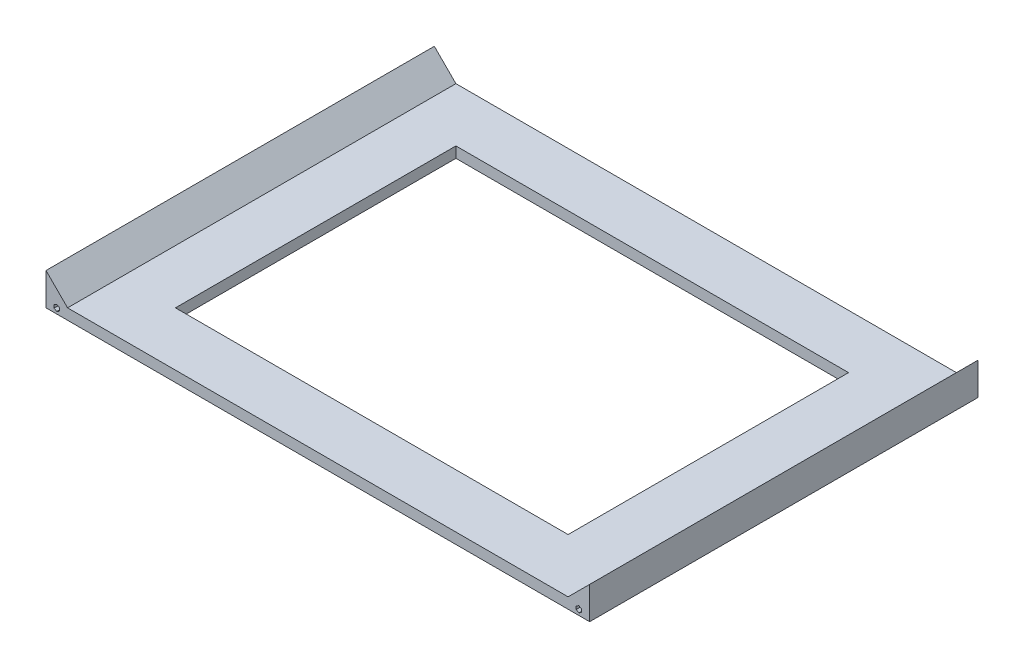
SolidWorks part; units mm, degrees
ref_plane "Front Plane" through (0, 0, 0) normal (0, 0, 1) x (1, 0, 0)
ref_plane "Top Plane" through (0, 0, 0) normal (0, 1, 0) x (1, 0, 0)
ref_plane "Right Plane" through (0, 0, 0) normal (1, 0, 0) x (0, 0, -1)
sketch "Sketch1" plane through (0, 0, 0) normal (0, 0, 1) x (1, 0, 0)
  line L0 (-126, 0) -> (126, 0)
  line L1 (-126, 0) -> (-126, 15)
  line L2 (-126, 15) -> (-116, 5)
  line L3 (-116, 5) -> (116, 5)
  line L4 (116, 5) -> (126, 15)
  line L5 (126, 15) -> (126, 0)
  point P2 (0, 0)
  dimension "D1" = 252
  dimension "D2" = 135
  dimension "D3" = 5
  dimension "D4" = 232
extrude "Boss-Extrude1" add sketch "Sketch1" along normal blind 90 and the other way blind 90
sketch "Sketch3" plane through (0, 0, 90) normal (0, 0, 1) x (1, 0, 0)
  line L0 (-126, 15) -> (-126, 0) construction
  line L1 (-121, 3.9434) -> (-122.25, 3.2217)
  line L2 (-122.25, 3.2217) -> (-122.25, 1.7783)
  line L3 (-122.25, 1.7783) -> (-121, 1.0566)
  line L4 (-121, 1.0566) -> (-119.75, 1.7783)
  line L5 (-119.75, 1.7783) -> (-119.75, 3.2217)
  line L6 (-119.75, 3.2217) -> (-121, 3.9434)
  line L7 (119.75, 3.2217) -> (121, 3.9434)
  line L8 (-126, 0) -> (126, 0) construction
  line L9 (119.75, 1.7783) -> (119.75, 3.2217)
  line L10 (0, -1000) -> (0, 49000) construction
  line L11 (121, 1.0566) -> (119.75, 1.7783)
  line L12 (122.25, 1.7783) -> (121, 1.0566)
  line L13 (122.25, 3.2217) -> (122.25, 1.7783)
  line L14 (121, 3.9434) -> (122.25, 3.2217)
  circle A0 centre (-121, 2.5) radius 1.25 construction
  dimension "D1" = 2.5
  dimension "D2" = 5
  dimension "D3" = 2.5
extrude "Cut-Extrude1" cut sketch "Sketch3" against normal through all
sketch "Sketch5" plane through (0, 5, 0) normal (0, 1, 0) x (1, 0, 0)
  line L8 (-91, 65) -> (-91, -65)
  line L9 (-91, -65) -> (91, -65)
  line L10 (91, -65) -> (91, 65)
  line L11 (91, 65) -> (-91, 65)
  line L12 (-91, 65) -> (-91, -65)
  line L13 (-91, -65) -> (91, -65)
  line L14 (91, -65) -> (91, 65)
  line L15 (91, 65) -> (-91, 65)
  dimension "D1" = 25
extrude "Cut-Extrude3" cut sketch "Sketch5" against normal through all
